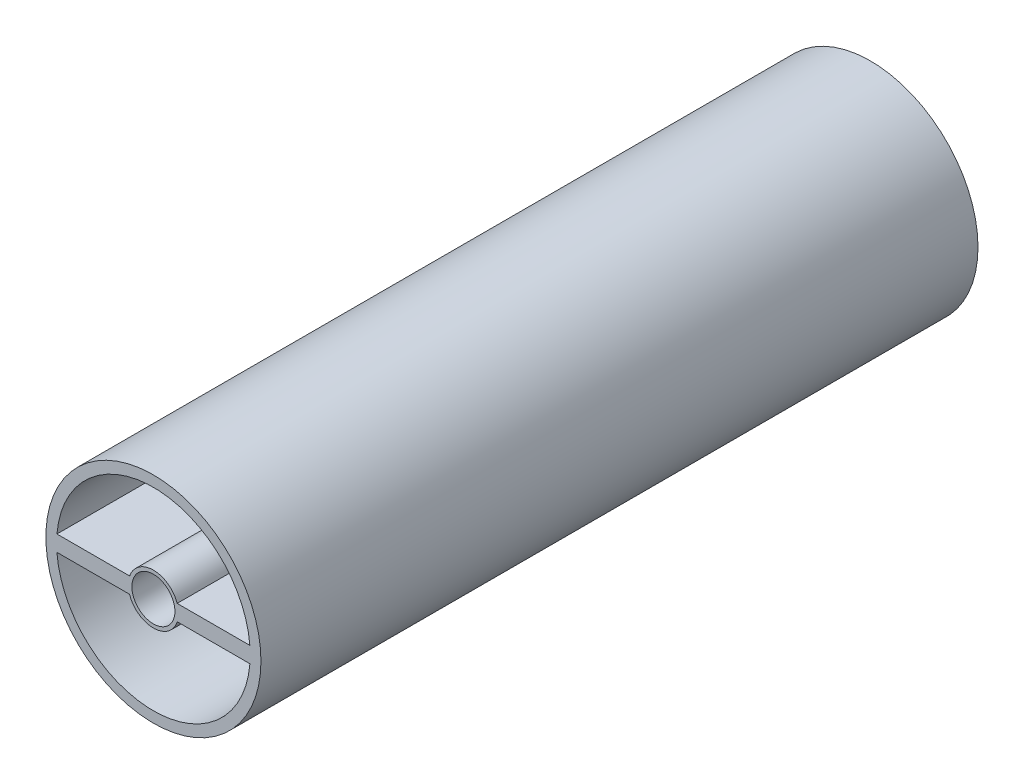
SolidWorks part; units mm, degrees
ref_plane "Front Plane" through (0, 0, 0) normal (0, 0, 1) x (1, 0, 0)
ref_plane "Top Plane" through (0, 0, 0) normal (0, 1, 0) x (1, 0, 0)
ref_plane "Right Plane" through (0, 0, 0) normal (1, 0, 0) x (0, 0, -1)
sketch "Sketch2" plane through (0, 0, 0) normal (0, 0, 1) x (1, 0, 0)
  line L0 (0, 13.5) -> (0, -13.5) construction
  line L3 (-13.4526, 1.1304) -> (-3.3124, 1.1304)
  line L5 (-13.4565, -1.0829) -> (-3.3283, -1.0829)
  line L6 (3.3124, 1.1304) -> (13.4526, 1.1304)
  line L7 (3.3283, -1.0829) -> (13.4565, -1.0829)
  circle A0 centre (0, 0) radius 15
  circle A3 centre (0, 0) radius 13.5
  arc A4 (-3.3283, -1.0829) -> (3.3283, -1.0829) centre (0, 0) ccw
  arc A5 (3.3124, 1.1304) -> (-3.3124, 1.1304) centre (0, 0) ccw
  circle A6 centre (0, 0) radius 3
  dimension "D1" = 30
  dimension "D2" = 27
  dimension "D3" = 7
  dimension "D6" = 6
  dimension "D4" = 10.1402
  dimension "D5" = 10.1282
extrude "Boss-Extrude5" add sketch "Sketch2" along normal blind 100 contours A5 L0 A6 A4 L7 A3 L6 | L0 A5 L3 A3 L5 A4 A6 | A0 A3 region at (7.2694, 0.0195, 0) region at (-7.2694, 0.0195, 0) region at (-14.5757, 0, 0)
